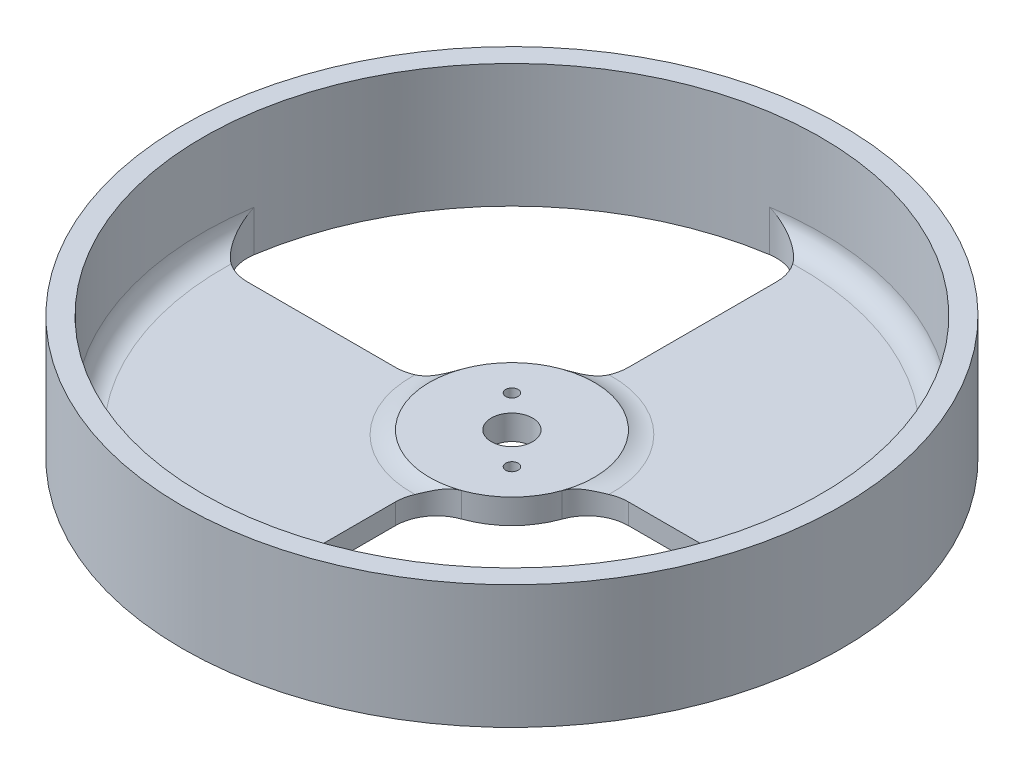
SolidWorks part; units mm, degrees
ref_plane "Front Plane" through (0, 0, 0) normal (0, 0, 1) x (1, 0, 0)
ref_plane "Top Plane" through (0, 0, 0) normal (0, 1, 0) x (1, 0, 0)
ref_plane "Right Plane" through (0, 0, 0) normal (1, 0, 0) x (0, 0, -1)
sketch "Sketch1" plane through (0, 0, 0) normal (0, 1, 0) x (1, 0, 0)
  line L1 (7.75, 7.75) -> (-7.75, 7.75) construction
  line L2 (7.75, 7.75) -> (7.75, -7.75) construction
  line L3 (7.75, -7.75) -> (-7.75, -7.75) construction
  line L4 (-7.75, 7.75) -> (-7.75, -7.75) construction
  line L29 (0, 75) -> (0, 20)
  line L30 (-20, 0) -> (-75, 0)
  line L31 (0, -75) -> (0, -20)
  line L32 (75, 0) -> (20, 0)
  circle A0 centre (0, 0) radius 5
  circle A1 centre (-7.75, 7.75) radius 1.5
  circle A2 centre (0, 0) radius 20
  circle A3 centre (7.75, 7.75) radius 1.5
  circle A4 centre (7.75, -7.75) radius 1.5
  circle A5 centre (-7.75, -7.75) radius 1.5
  circle A18 centre (0, 0) radius 80
  circle A19 centre (0, 0) radius 75
  dimension "D2" = 10
  dimension "D5" = 7.75
  dimension "D6" = 3
  dimension "D9" = 40
  dimension "D10" = 160
  dimension "D7" = 5
  dimension "D3" = 15.5
  dimension "D4" = 7.75
extrude "Boss-Extrude1" add sketch "Sketch1" along normal blind 6 contours A2 | A3 | A5 region at (13.7421, 0, -13.7421) region at (7.75, 0, -7.75) region at (-7.75, 0, 7.75)
extrude "Boss-Extrude2" add sketch "Sketch1<5>" along normal blind 5 contours L32 A19 L29 A2 | L30 A19 L31 A2 region at (33.618, 0, -33.618) region at (-33.618, 0, 33.618)
sketch "Sketch1<5>" plane through (0, 0, 0) normal (0, 1, 0) x (1, 0, 0) same geometry as "Sketch1"
extrude "Boss-Extrude3" add sketch "Sketch1<6>" along normal blind 30 contours A18 A19 region at (-77.7373, 0, 0)
sketch "Sketch1<6>" plane through (0, 0, 0) normal (0, 1, 0) x (1, 0, 0) same geometry as "Sketch1"
fillet "Fillet1" radius 5 2 edges at (-53.033, 5, 53.033) (53.033, 5, -53.033)
fillet "Fillet2" radius 10 8 edges at (0, 2.5, 20) (20, 2.5, 0) (0, 2.5, -20) (-20, 2.5, 0) (0, 5, -75) (75, 5, 0) (0, 5, 75) (-75, 5, 0)
fillet "Fillet3" radius 10 2 edges at (14.1421, 5, -14.1421) (-14.1421, 5, 14.1421)
sketch "Sketch2" plane through (0, 0, 0) normal (0, -1, 0) x (1, 0, 0)
  circle A0 centre (-7.75, -7.75) radius 3
  circle A1 centre (7.75, 7.75) radius 3
  dimension "D1" = 6
extrude "Cut-Extrude1" cut sketch "Sketch2" against normal blind 3
